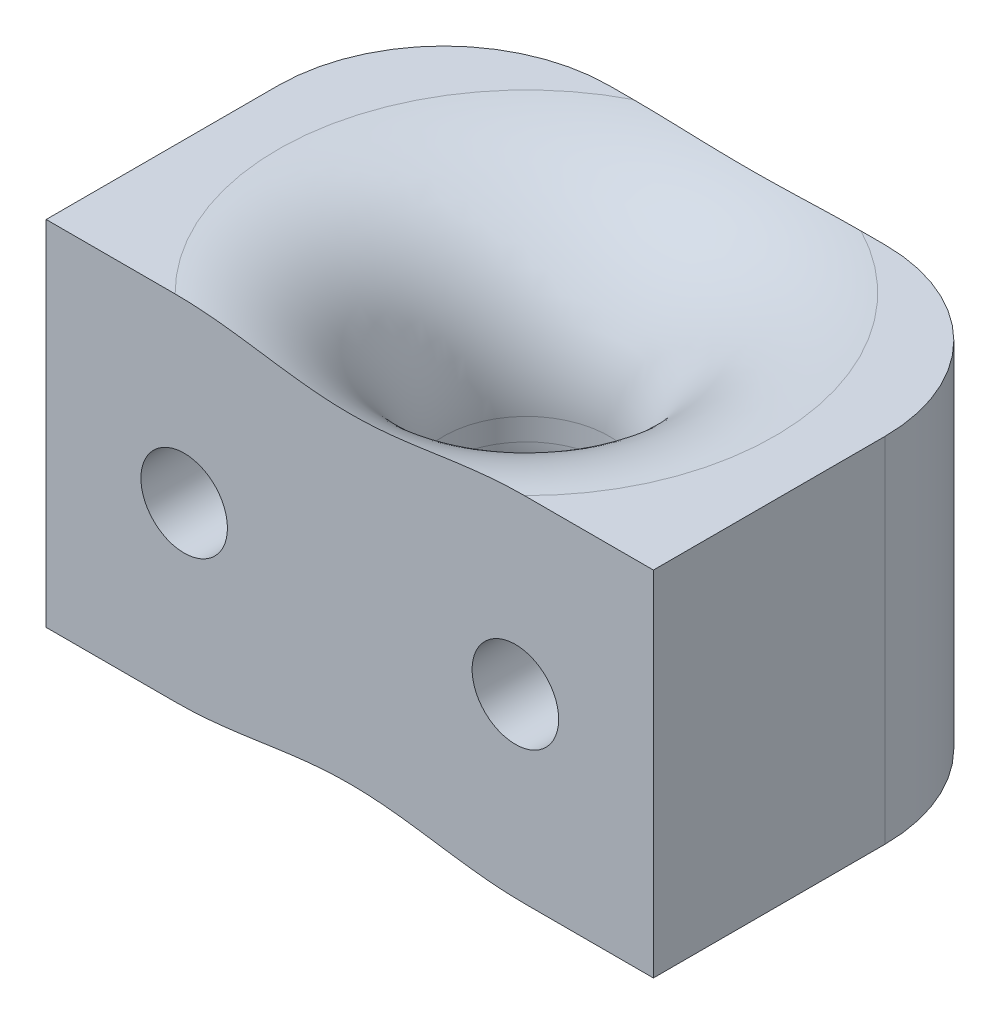
SolidWorks part; units mm, degrees
material "Delrin 2700 NC010, Low Viscosity Acetal Copolymer (SS)"
ref_plane "Front Plane" through (0, 0, 0) normal (0, 0, 1) x (1, 0, 0)
ref_plane "Top Plane" through (0, 0, 0) normal (0, 1, 0) x (1, 0, 0)
ref_plane "Right Plane" through (0, 0, 0) normal (1, 0, 0) x (0, 0, -1)
sketch "Sketch2" plane through (0, 0, 0) normal (0, 0, 1) x (1, 0, 0)
  line L0 (0, 10.16) -> (-7.9375, 10.16) construction
  line L1 (0, 0) -> (-34.925, 0)
  line L2 (0, 0) -> (0, 20.32)
  line L3 (0, 20.32) -> (-34.925, 20.32)
  line L4 (-34.925, 0) -> (-34.925, 20.32)
  line L5 (-7.9375, 10.16) -> (-26.9875, 10.16) construction
  line L6 (-26.9875, 10.16) -> (-34.925, 10.16) construction
  circle A0 centre (-7.9375, 10.16) radius 2.4892
  circle A1 centre (-26.9875, 10.16) radius 2.4892
  dimension "D3" = 4.9784
  dimension "D1" = 20.32
  dimension "D2" = 34.925
  dimension "D4" = 19.05
extrude "Boss-Extrude1" add sketch "Sketch2" along normal blind 10.16 and the other way blind 12.7
sketch "Sketch3" plane through (0, 0, 0) normal (0, -1, 0) x (1, 0, 0)
  line L0 (-34.925, 0) -> (-17.4625, 0) construction
  line L2 (-17.4625, 0) -> (0, 0) construction
  line L4 (-34.925, -12.7) -> (-34.925, 10.16) construction
  circle A0 centre (-17.4625, 0) radius 4.7625
  point P4 (-31.75, -0.6107)
  point P6 (0, 0)
  dimension "D1" = 9.525
extrude "Cut-Extrude1" cut sketch "Sketch3" against normal through all
sketch "Sketch4" plane through (0, 0, 0) normal (0, 0, 1) x (1, 0, 0)
  line L0 (-22.225, 20.32) -> (-22.225, 0) construction
  line L3 (-12.7, 20.32) -> (-22.225, 20.32) construction
  line L4 (-31.75, 20.32) -> (-17.4625, 20.32)
  line L5 (-17.4625, 20.32) -> (-17.4625, 0)
  line L6 (-17.4625, 0) -> (-31.75, 0)
  line L7 (-22.225, 9.525) -> (-22.225, 10.795)
  line L8 (-17.4625, 20.32) -> (-17.4625, -13.8225) construction
  line L9 (-34.925, 0) -> (0, 0) construction
  arc A0 (-31.75, 20.32) -> (-22.225, 10.795) centre (-31.75, 10.795) cw
  arc A1 (-31.75, 0) -> (-22.225, 9.525) centre (-31.75, 9.525) ccw
  point P14 (0, 0)
  point P17 (0, 0)
  dimension "D1" = 9.525
revolve "Cut-Revolve1" cut sketch "Sketch4" angle 360 about L8
hole_wizard "CBORE for #10 Socket Head Cap Screw1" positions "Sketch5" profile "Sketch7" counterbore size "#10" standard "ANSI Inch" end condition through all
sketch "Sketch5" plane through (0, 0, -12.7) normal (0, 0, -1) x (-1, 0, 0)
  point P0 (26.9875, 10.16)
  point P3 (7.9375, 10.16)
sketch "Sketch7" plane through (-26.9875, 10.16, -12.7) normal (1, 0, 0) x (0, 1, 0)
  line L0 (0, 0) -> (0, 22.86)
  line L1 (0, 22.86) -> (2.4892, 22.86)
  line L3 (2.4892, 22.86) -> (2.4892, 4.826)
  line L4 (2.4892, 4.826) -> (4.7625, 4.826)
  line L5 (4.7625, 4.826) -> (4.7625, 0)
  line L7 (4.7625, 0) -> (0, 0)
  line L11 (0, -6.35) -> (0, 107.95) construction
  dimension "Thru Hole Dia." = 4.9784
  dimension "Thru Hole Depth" = 22.86
  dimension "C'Bore Dia." = 9.525
  dimension "C'Bore Depth" = 4.826
fillet "Fillet1" radius 9.525 2 edges at (0, 10.16, -12.7) (-34.925, 10.16, -12.7)
